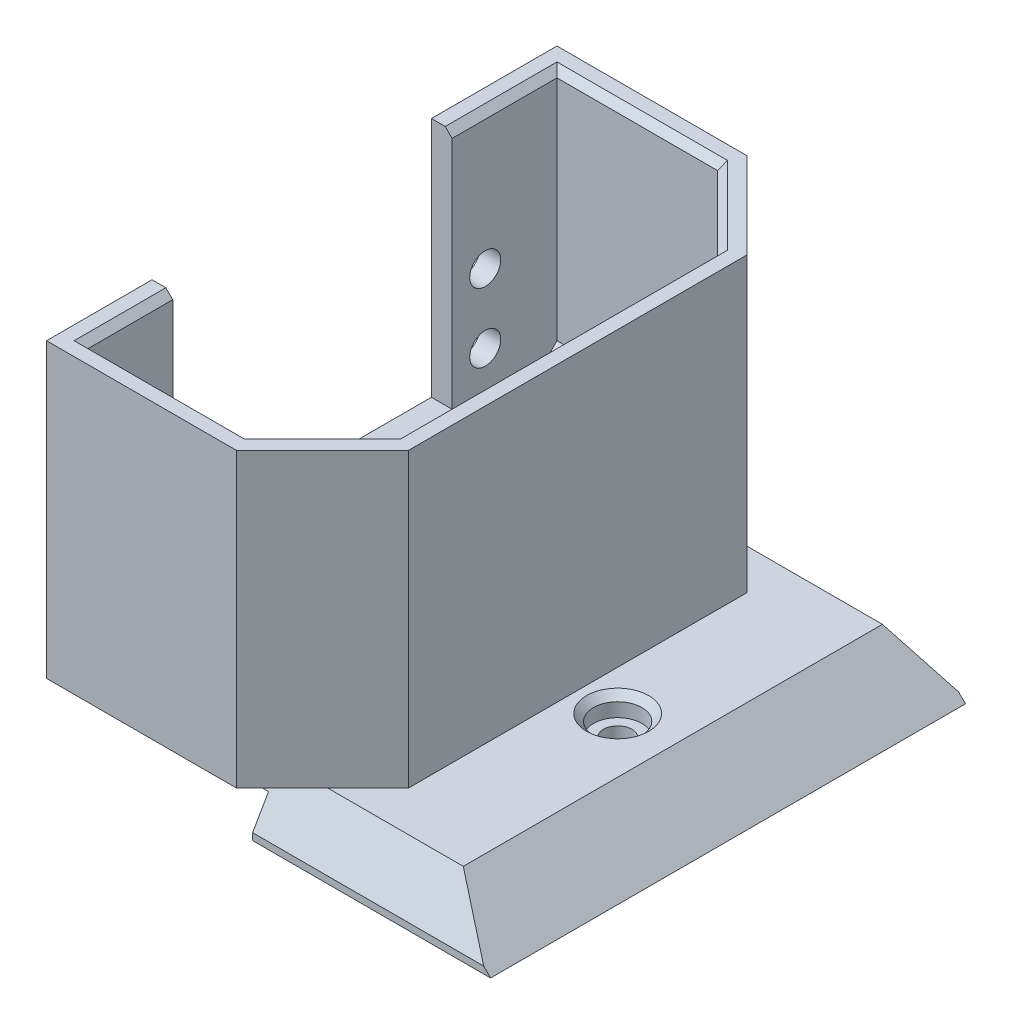
SolidWorks part; units mm, degrees
material "ABS"
ref_plane "Front Plane" through (0, 0, 0) normal (0, 0, 1) x (1, 0, 0)
ref_plane "Top Plane" through (0, 0, 0) normal (0, 1, 0) x (1, 0, 0)
ref_plane "Right Plane" through (0, 0, 0) normal (1, 0, 0) x (0, 0, -1)
sketch "Sketch1" plane through (0, 0, 0) normal (0, 1, 0) x (1, 0, 0)
  line L1 (-20, 35) -> (7.5426, 35)
  line L2 (-20, 35) -> (-20, -39)
  line L3 (-20, -39) -> (7.5426, -39)
  line L4 (20, 22.5426) -> (20, -26.5426)
  line L8 (7.5426, 35) -> (20, 22.5426)
  line L9 (7.5426, -39) -> (20, -26.5426)
  line L10 (20, 18.3) -> (3.3, 35) construction
  dimension "D4" = 20
  dimension "D5" = 3
  dimension "D3" = 16.7
  dimension "D2" = 35
  dimension "D6" = 74
  dimension "D1" = 40
extrude "Main Face Extrude" add sketch "Sketch1" along normal blind 7.4
sketch "Sketch3" plane through (0, 7.4, 0) normal (0, 1, 0) x (1, 0, 0)
  line L4 (-20, 35) -> (-20, -39)
  line L5 (-20, -39) -> (7.5426, -39)
  line L6 (20, -26.5426) -> (20, 22.5426)
  line L7 (7.5426, 35) -> (-20, 35)
  line L8 (-20, 35) -> (-20, -39)
  line L9 (-20, -39) -> (7.5426, -39)
  line L10 (20, -26.5426) -> (20, 22.5426)
  line L11 (7.5426, 35) -> (-20, 35)
  line L12 (-17, 32) -> (-17, -36)
  line L13 (-17, -36) -> (6.3, -36)
  line L14 (6.3, -36) -> (17, -25.3)
  line L15 (17, -25.3) -> (17, 21.3)
  line L16 (17, 21.3) -> (6.3, 32)
  line L17 (6.3, 32) -> (-17, 32)
  line L18 (7.5426, -39) -> (20, -26.5426)
  line L19 (7.5426, -39) -> (20, -26.5426)
  line L20 (20, 22.5426) -> (7.5426, 35)
  line L21 (20, 22.5426) -> (7.5426, 35)
  dimension "D1" = 0
  dimension "D2" = 3
extrude "Main Walls Extrude" add sketch "Sketch3" along normal blind 35
chamfer "Main Walls Lower Chamfer" distance 1 angle 45 5 edges at (-5.35, 7.4, 36) (11.65, 7.4, 30.65) (17, 7.4, 2) (11.65, 7.4, -26.65) (-5.35, 7.4, -32)
chamfer "Main Walls Entry Chamfer" distance 1 angle 45 6 edges at (-5.35, 42.4, 36) (11.65, 42.4, 30.65) (17, 42.4, 2) (11.65, 42.4, -26.65) (-17, 42.4, 2) (-5.35, 42.4, -32)
sketch "Sketch4" plane through (0, 42.4, 0) normal (0, 1, 0) x (1, 0, 0)
  line L0 (-17, 32) -> (-17, -36) construction
  line L1 (-17, 16.8) -> (-20, 16.8)
  line L2 (-17, 16.8) -> (-17, -23.7)
  line L3 (-17, -23.7) -> (-20, -23.7)
  line L4 (-20, 16.8) -> (-20, -23.7)
  line L5 (-20, 35) -> (-20, -39) construction
  point P8 (-17, -3.45)
  dimension "D1" = 40.5
  dimension "D2" = 3.45
extrude "Servo Mount Cut" cut sketch "Sketch4" against normal up to surface (35 mm away) up to face at (1.6286, 7.4, 2)
sketch "Sketch5" plane through (-20, 0, 0) normal (-1, 0, 0) x (0, 0, 1)
  line L2 (-21.6, 22.65) -> (-16.8, 22.65) construction
  line L3 (-16.8, 7.4) -> (-16.8, 42.4) construction
  line L4 (28.5, 22.65) -> (23.7, 22.65) construction
  line L5 (23.7, 7.4) -> (23.7, 42.4) construction
  line L6 (25.3, 7.4) -> (-21.3, 7.4) construction
  circle A0 centre (-21.6, 22.65) radius 2.25
  circle A1 centre (-21.6, 12.65) radius 2.25
  circle A2 centre (28.5, 22.65) radius 2.25
  circle A3 centre (28.5, 12.65) radius 2.25
  dimension "D1" = 4.5
  dimension "D2" = 10
  dimension "D3" = 50.1
  dimension "D4" = 5.25
extrude "Servo Mount Holes" cut sketch "Sketch5" against normal up to next
sketch "Sketch8" plane through (-20, 0, 0) normal (-1, 0, 0) x (0, 0, 1)
  line L0 (-28.3812, 0) -> (-32.4226, -7)
  line L1 (-35, 0) -> (39, 0) construction
  line L3 (-32.4226, -8) -> (36.4226, -8)
  line L5 (36.4226, -7) -> (32.3812, 0)
  line L6 (32.3812, 0) -> (-28.3812, 0)
  line L7 (2, -8) -> (2, 0) construction
  line L8 (-32.4226, -8) -> (-32.4226, -7)
  line L9 (36.4226, -8) -> (36.4226, -7)
  line L11 (-33, -8) -> (-32.4226, -8) construction
  line L12 (-32.4226, -7) -> (-33, -8) construction
  line L13 (36.4226, -8) -> (37, -8) construction
  line L14 (37, -8) -> (36.4226, -7) construction
  point P12 (2, 0)
  dimension "D1" = 60
  dimension "D2" = 8
  dimension "D3" = 1
  dimension "D4" = 70
extrude "Mount Dovetail" add sketch "Sketch8" against normal blind 61.8
chamfer "Mount Dovetail Chamfer" distance 8 angle 45 1 edges at (41.8, 0, 2)
sketch "Sketch9" plane through (0, -8, 0) normal (0, -1, 0) x (1, 0, 0)
  line L0 (41.8, -32.4226) -> (-20, -32.4226) construction
  line L1 (-20, 36.4226) -> (7.3, 36.4226)
  line L2 (-20, 36.4226) -> (-20, -32.4226)
  line L3 (-20, -32.4226) -> (7.3, -32.4226)
  line L4 (7.3, 36.4226) -> (7.3, -32.4226)
  dimension "D1" = 27.3
extrude "Dovetail Offset Cut" cut sketch "Sketch9" against normal blind 5
sketch "Sketch10" plane through (0, 0, 0) normal (0, 1, 0) x (1, 0, 0)
  line L0 (41.8, 32.4226) -> (41.8, -36.4226) construction
  line L1 (41.8, -2) -> (25.8, -2) construction
  circle A0 centre (25.8, -2) radius 2.05
  dimension "D2" = 4.1
  dimension "D1" = 16
extrude "Mount Screw Hole" cut sketch "Sketch10" against normal through all
sketch "Sketch11" plane through (0, 0, 0) normal (0, 1, 0) x (1, 0, 0)
  circle A0 centre (25.8, -2) radius 3.5
  dimension "D1" = 7
extrude "Mount Screw Countersink" cut sketch "Sketch11" against normal blind 3
chamfer "Mount Screw Countersink Chamfer" distance 1 angle 45 1 edges at (25.8, 0, 5.5)
sketch "Sketch2" plane through (0, 7.4, 0) normal (0, 1, 0) x (1, 0, 0)
  line L0 (-20, 35) -> (-20, 16.8) construction
  line L1 (-1.7, 26.5) -> (5.3, 26.5)
  line L2 (-3.7, 24.5) -> (-3.7, -11.5)
  line L3 (-1.7, -13.5) -> (5.3, -13.5)
  line L4 (7.3, 24.5) -> (7.3, -11.5)
  line L6 (-3.7, 24.5) -> (-1.7, 26.5)
  line L7 (-3.7, -11.5) -> (-1.7, -13.5)
  line L8 (5.3, -13.5) -> (7.3, -11.5)
  line L9 (5.3, 26.5) -> (7.3, 24.5)
  line L11 (1.8, 26.5) -> (1.8, -13.5) construction
  line L13 (-3.7, 6.5) -> (7.3, 6.5) construction
  line L15 (-20, -23.7) -> (-20, 16.8) construction
  point P3 (-20, -3.45)
  point P4 (1.8, 26.5)
  dimension "D1" = 11
  dimension "D2" = 40
  dimension "D3" = 21.8
  dimension "D4" = 9.95
  dimension "D5" = 2
  dimension "D6" = 2
extrude "Gear Cut" cut sketch "Sketch2" against normal through all
chamfer "Gear Entry Chamfer" distance 3 angle 45 8 edges at (6.3, 7.4, 12.5) (1.8, 7.4, 13.5) (-2.7, 7.4, 12.5) (-3.7, 7.4, -6.5) (-2.7, 7.4, -25.5) (7.3, 7.4, -6.5) (6.3, 7.4, -25.5) (1.8, 7.4, -26.5)
ref_plane "Gear Plane" through (1.8, 0, 0) normal (-1, 0, 0) x (0, 0, 1)
sketch "Reference Gear Shape" plane through (1.8, 0, 0) normal (-1, 0, 0) x (0, 0, 1)
  line L0 (-1006.3434, -4.35) -> (48993.6566, -4.35) construction
  circle A0 centre (-6.5, 17.65) radius 23
  circle A1 centre (-21.6, 22.65) radius 2.25 construction
  dimension "D1" = 46
  dimension "D2" = 15.1
  dimension "D3" = 5
  dimension "D4" = 22
equation "\"D4@Sketch1\"=\"D1@Sketch1\"/2"
